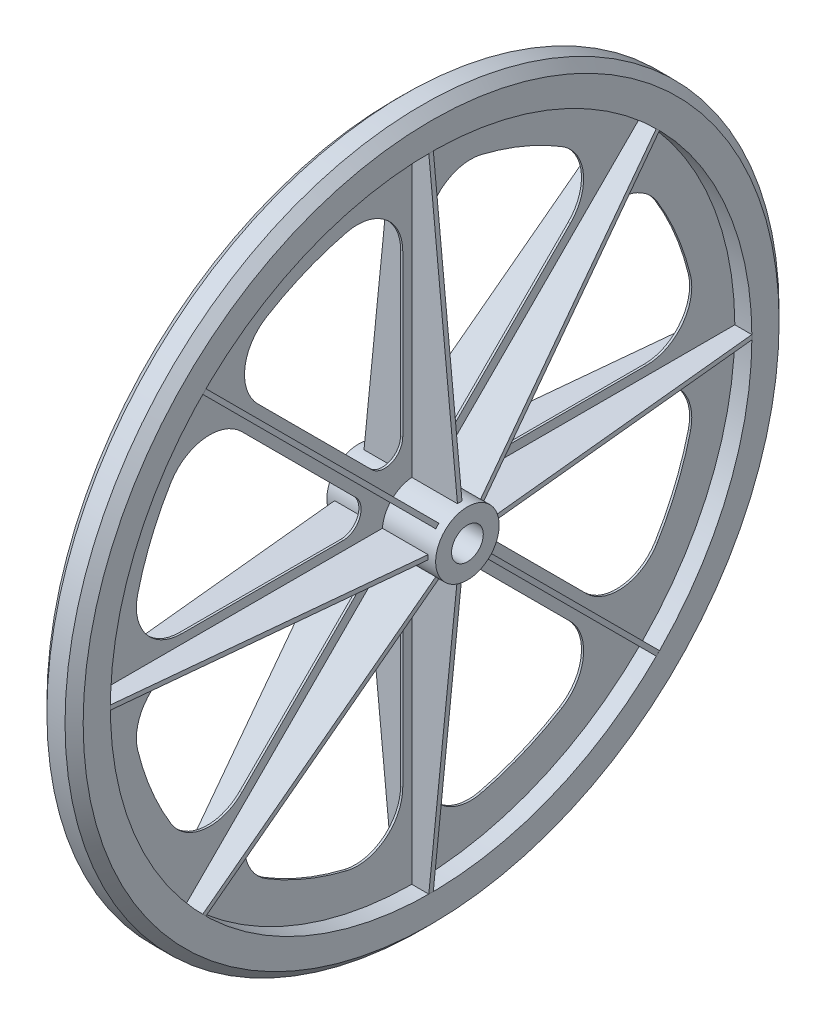
SolidWorks part; units mm, degrees
ref_plane "Front Plane" through (0, 0, 0) normal (0, 0, 1) x (1, 0, 0)
ref_plane "Top Plane" through (0, 0, 0) normal (0, 1, 0) x (1, 0, 0)
ref_plane "Right Plane" through (0, 0, 0) normal (1, 0, 0) x (0, 0, -1)
sketch "Sketch1" plane through (0, 0, 0) normal (1, 0, 0) x (0, 0, -1)
  circle A0 centre (0, 0) radius 22.225
  dimension "D2" = 44.45
extrude "Boss-Extrude1" add sketch "Sketch1" along normal blind 38.1 and the other way blind 38.1
sketch "Sketch2" plane through (0, 0, 0) normal (1, 0, 0) x (0, 0, -1)
  circle A0 centre (0, 0) radius 250
  dimension "D1" = 500
extrude "Boss-Extrude2" add sketch "Sketch2" along normal blind 0.762 and the other way blind 0.762
sketch "Sketch3" plane through (0, 0, 0) normal (1, 0, 0) x (0, 0, -1)
  circle A0 centre (0, 0) radius 250 construction
  circle A1 centre (0, 0) radius 250
  circle A2 centre (0, 0) radius 224.6
  dimension "D1" = 25.4
extrude "Boss-Extrude3" add sketch "Sketch3" along normal blind 12.7 and the other way blind 12.7
sketch "Sketch4" plane through (0, 0, 0) normal (1, 0, 0) x (0, 0, -1)
  line L0 (0, 250) -> (0, -250) construction
  line L1 (-250, 0) -> (250, 0) construction
  line L2 (-176.7767, -176.7767) -> (176.7767, 176.7767) construction
  line L3 (-176.7767, 176.7767) -> (176.7767, -176.7767) construction
  line L4 (109.4187, 120.644) -> (29.6178, 40.8431)
  line L5 (7.9375, 162.6788) -> (7.9375, 49.8233)
  circle A0 centre (0, 0) radius 250 construction
  circle A1 centre (0, 0) radius 250 construction
  arc A2 (47.2126, 193.5242) -> (103.4579, 170.2266) centre (0, 0) cw
  arc A3 (29.6178, 40.8431) -> (7.9375, 49.8233) centre (20.6375, 49.8233) cw
  arc A4 (103.4579, 170.2266) -> (109.4187, 120.644) centre (86.968, 143.0946) cw
  arc A5 (47.2126, 193.5242) -> (7.9375, 162.6788) centre (39.6875, 162.6788) ccw
  dimension "D4" = 50.8
  dimension "D5" = 12.7
  dimension "D6" = 31.75
  dimension "D1" = 45
  dimension "D2" = 15.875
  dimension "D3" = 15.875
extrude "Cut-Extrude1" cut sketch "Sketch4" against normal through all and the other way through all
sketch "Sketch5" plane through (0, 0, 0) normal (0, 1, 0) x (1, 0, 0)
  line L1 (-34.925, -1.5875) -> (34.925, -1.5875)
  line L2 (-34.925, -1.5875) -> (-34.925, 1.5875)
  line L3 (-34.925, 1.5875) -> (34.925, 1.5875)
  line L4 (34.925, -1.5875) -> (34.925, 1.5875)
  line L5 (-34.925, -1.5875) -> (34.925, 1.5875) construction
  line L6 (-34.925, 1.5875) -> (34.925, -1.5875) construction
  line L7 (38.1, -22.225) -> (38.1, 22.225) construction
  point P0 (0, 0)
  dimension "D1" = 3.175
  dimension "D2" = 3.175
ref_plane "Plane1" through (0, 240, 0) normal (0, 1, 0) x (-1, 0, 0)
sketch "Sketch6" plane through (0, 240, 0) normal (0, 1, 0) x (-1, 0, 0)
  line L1 (11.1125, 1.5875) -> (-11.1125, 1.5875)
  line L2 (11.1125, 1.5875) -> (11.1125, -1.5875)
  line L3 (11.1125, -1.5875) -> (-11.1125, -1.5875)
  line L4 (-11.1125, 1.5875) -> (-11.1125, -1.5875)
  line L5 (11.1125, 1.5875) -> (-11.1125, -1.5875) construction
  line L6 (11.1125, -1.5875) -> (-11.1125, 1.5875) construction
  point P0 (0, 0)
  dimension "D1" = 22.225
  dimension "D2" = 3.175
loft "Loft1" add profiles "Sketch5", "Sketch6" connector at (-34.925, 0, 1.5875) connector at (-11.1125, 240, 1.5875)
pattern_circular "CirPattern1" count 8 over 360 about axis through (-38.1, 0, 0) along (1, 0, 0) of "Cut-Extrude1", "Loft1"
sketch "Sketch9" plane through (0, 0, 0) normal (1, 0, 0) x (0, 0, -1)
  circle A0 centre (0, 0) radius 11.1125
  dimension "D1" = 22.225
extrude "Cut-Extrude2" cut sketch "Sketch9" against normal through all and the other way through all
chamfer "Chamfer1" distance 6.35 angle 45 2 edges at (-12.7, 0, -250) (12.7, 0, -250)
